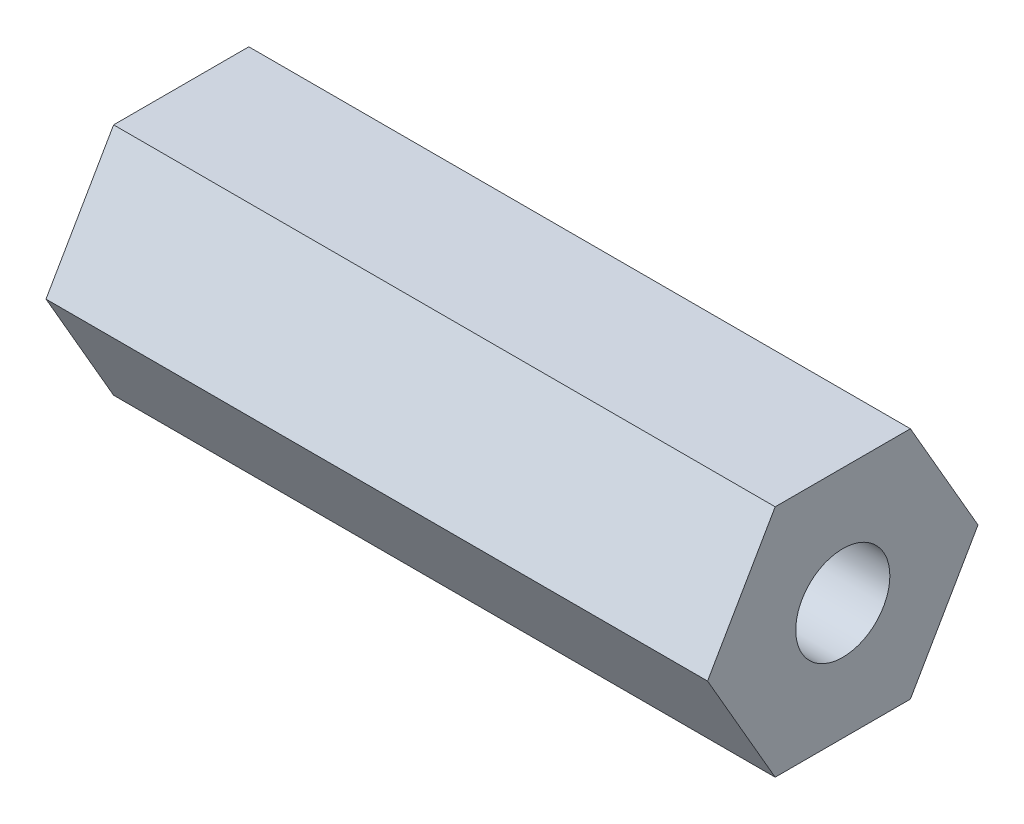
SolidWorks part; units mm, degrees
ref_plane "Front" through (0, 0, 0) normal (0, 0, 1) x (1, 0, 0)
ref_plane "Top" through (0, 0, 0) normal (0, 1, 0) x (1, 0, 0)
ref_plane "Right" through (0, 0, 0) normal (1, 0, 0) x (0, 0, -1)
sketch "Sketch1" plane through (0, 0, 0) normal (1, 0, 0) x (0, 0, -1)
  line L1 (7.3323, 0) -> (3.6662, 6.35)
  line L2 (3.6662, 6.35) -> (-3.6662, 6.35)
  line L3 (-3.6662, 6.35) -> (-7.3323, 0)
  line L4 (-7.3323, 0) -> (-3.6662, -6.35)
  line L5 (-3.6662, -6.35) -> (3.6662, -6.35)
  line L6 (3.6662, -6.35) -> (7.3323, 0)
  circle A0 centre (0, 0) radius 6.35 construction
  dimension "D1" = 12.7
extrude "Boss-Extrude1" add sketch "Sketch1" along normal mid plane 35.875
ref_axis "Axis1" through (-80.9, 0, 0) along (1, 0, 0)
hole_wizard "1/4-20 Tapped Hole1" positions "Sketch2" profile "Sketch3" tap size "1/4-20" standard "ANSI Inch" end condition through all
sketch "Sketch2" plane through (17.9375, 0, 0) normal (1, 0, 0) x (0, 0, -1)
  point P0 (0, 0)
sketch "Sketch3" plane through (17.9375, 0, 0) normal (0, 1, 0) x (0, 0, -1)
  line L0 (0, 0) -> (0, 35.875)
  line L1 (0, 35.875) -> (2.5527, 35.875)
  line L2 (2.5527, 35.875) -> (2.5527, 0)
  line L5 (2.5527, 0) -> (0, 0)
  line L11 (0, -6.35) -> (0, 107.95) construction
  dimension "Thru Tap Drill Dia." = 5.1054
  dimension "Thru Tap Drill Depth" = 35.875
cosmetic thread "Hole Thread1" parameters "D2"=6.35
